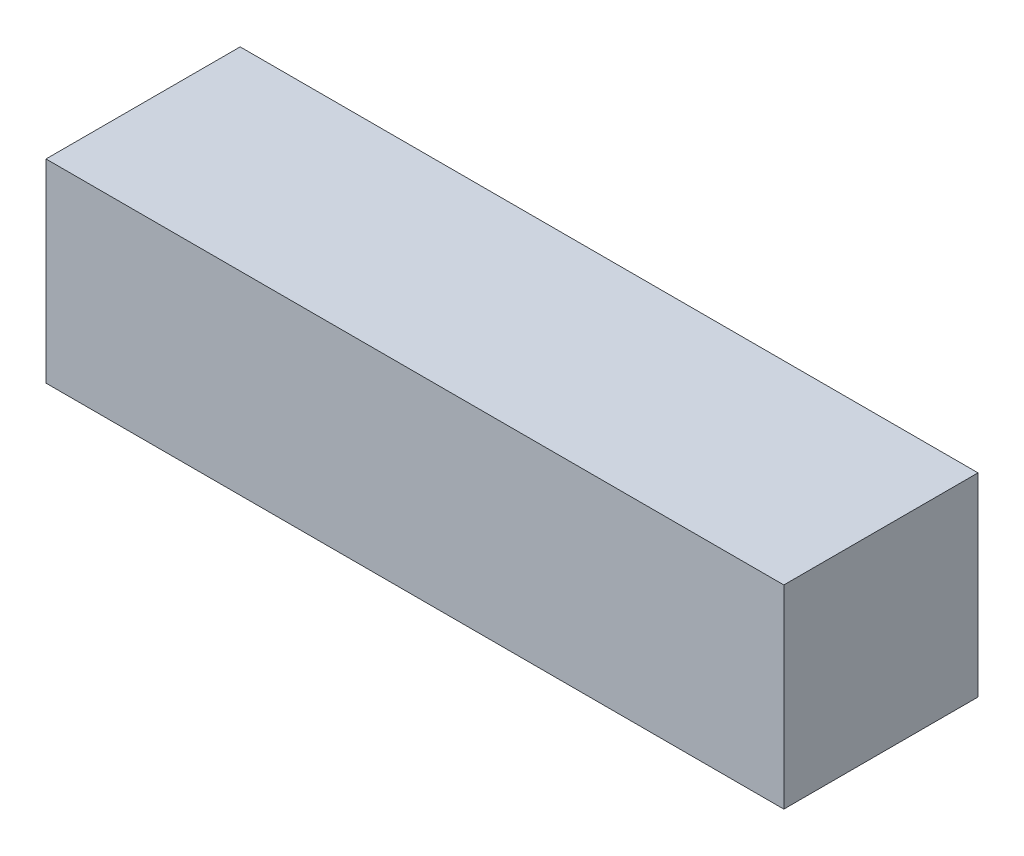
SolidWorks part; units mm, degrees
ref_plane "Front Plane" through (0, 0, 0) normal (0, 0, 1) x (1, 0, 0)
ref_plane "Top Plane" through (0, 0, 0) normal (0, 1, 0) x (1, 0, 0)
ref_plane "Right Plane" through (0, 0, 0) normal (1, 0, 0) x (0, 0, -1)
sketch "Sketch1" plane through (0, 0, 0) normal (0, 1, 0) x (1, 0, 0)
  line L1 (0, 0) -> (-152, 0)
  line L2 (0, 0) -> (0, -40)
  line L3 (0, -40) -> (-152, -40)
  line L4 (-152, 0) -> (-152, -40)
  dimension "D1" = 40
  dimension "D2" = 152
extrude "Boss-Extrude1" add sketch "Sketch1" along normal blind 40
